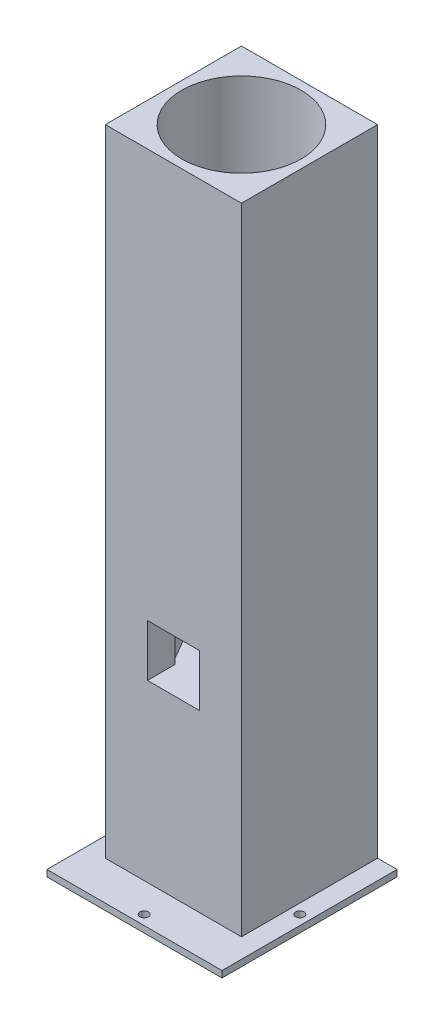
SolidWorks part; units mm, degrees
ref_plane "Front Plane" through (0, 0, 0) normal (0, 0, 1) x (1, 0, 0)
ref_plane "Top Plane" through (0, 0, 0) normal (0, 1, 0) x (1, 0, 0)
ref_plane "Right Plane" through (0, 0, 0) normal (1, 0, 0) x (0, 0, -1)
sketch "Sketch2" plane through (0, 0, 0) normal (0, 1, 0) x (1, 0, 0)
  line L0 (-7.1, 17.2376) -> (7.1, 17.2376)
  line L1 (11.3782, 14.7676) -> (18.4782, 2.47)
  line L2 (18.4782, -2.47) -> (11.3782, -14.7676)
  line L3 (7.1, -17.2376) -> (-7.1, -17.2376)
  line L4 (-11.3782, -14.7676) -> (-18.4782, -2.47)
  line L5 (-18.4782, 2.47) -> (-11.3782, 14.7676)
  line L6 (-7.1, 17.2376) -> (-11.3782, 14.7676)
  line L7 (11.3782, 14.7676) -> (7.1, 17.2376)
  line L8 (18.4782, -2.47) -> (18.4782, 2.47)
  line L9 (7.1, -17.2376) -> (11.3782, -14.7676)
  line L10 (-11.3782, -14.7676) -> (-7.1, -17.2376)
  line L11 (-18.4782, 2.47) -> (-18.4782, -2.47)
  line L13 (-26.25, -26.25) -> (26.25, -26.25)
  line L14 (-26.25, -26.25) -> (-26.25, 26.25)
  line L15 (-26.25, 26.25) -> (26.25, 26.25)
  line L16 (26.25, -26.25) -> (26.25, 26.25)
  line L17 (-26.25, -26.25) -> (26.25, 26.25) construction
  line L18 (-26.25, 26.25) -> (26.25, -26.25) construction
  circle A0 centre (0, 0) radius 28.6425
  circle A1 centre (0, 0) radius 18.6425 construction
  circle A2 centre (0, 0) radius 23
  point P5 (0, 17.2376)
  point P16 (0, 0)
  dimension "D5" = 10
  dimension "D6" = 46
  dimension "D7" = 52.5
  dimension "D1" = 14.2
  dimension "D2" = 4.94
  dimension "D3" = 6
  dimension "D8" = 52.5
  dimension "D4" = 6
extrude "Boss-Extrude1" add sketch "Sketch2" along normal blind 50 contours A0 A2 | A2 L11 L5 L6 L0 L7 L1 L8 L2 L9 L3 L10 L4 region at (-19.7283, 0, 19.7283) region at (-22.3495, 0, 0)
extrude "Boss-Extrude2" add sketch "Sketch2<3>" along normal blind 127.5 from surface contours A0 A2 region at (-19.7283, 0, 19.7283) starting at face at (0, 50, 0)
sketch "Sketch2<3>" plane through (0, 0, 0) normal (0, 1, 0) x (1, 0, 0) same geometry as "Sketch2"
extrude "Boss-Extrude3" add sketch "Sketch2<4>" along normal up to surface (177.5 mm away) contours A0 L15 L14 | A0 L16 L15 | A0 L13 L16 | A0 L14 L13 region at (-21.968, 0, 21.968) region at (21.968, 0, 21.968) region at (-21.968, 0, -21.968) region at (21.968, 0, -21.968) up to face at (0, 177.5, 0)
sketch "Sketch2<4>" plane through (0, 0, 0) normal (0, 1, 0) x (1, 0, 0) same geometry as "Sketch2"
sketch "Sketch3" plane through (0, 0, 0) normal (0, -1, 0) x (1, 0, 0)
  line L1 (-26.25, 26.25) -> (26.25, 26.25)
  line L2 (-26.25, 26.25) -> (-26.25, -26.25)
  line L3 (-26.25, -26.25) -> (26.25, -26.25)
  line L4 (26.25, 26.25) -> (26.25, -26.25)
extrude "Boss-Extrude4" add sketch "Sketch3" along normal blind 70
ref_plane "Plane1" through (0, -70, 0) normal (0, -1, 0) x (-1, 0, 0)
sketch "Sketch5" plane through (0, -70, 0) normal (0, -1, 0) x (1, 0, 0)
  line L0 (26.25, 26.25) -> (-26.25, 26.25) construction
  line L1 (-33.75, -26.25) -> (33.75, -26.25)
  line L2 (-33.75, -26.25) -> (-33.75, 41.25)
  line L3 (-33.75, 41.25) -> (33.75, 41.25)
  line L4 (33.75, -26.25) -> (33.75, 41.25)
  line L5 (-33.75, -26.25) -> (33.75, 41.25) construction
  line L6 (-33.75, 41.25) -> (33.75, -26.25) construction
  line L7 (-23.75, -23.75) -> (23.75, -23.75)
  line L8 (-23.75, -23.75) -> (-23.75, 23.75)
  line L9 (-23.75, 23.75) -> (23.75, 23.75)
  line L10 (23.75, -23.75) -> (23.75, 23.75)
  line L11 (-23.75, -23.75) -> (23.75, 23.75) construction
  line L12 (-23.75, 23.75) -> (23.75, -23.75) construction
  line L13 (0, -994.535) -> (0, 49005.465) construction
  line L14 (-26.25, -26.25) -> (26.25, -26.25) construction
  circle A1 centre (0, 37.5) radius 1.65
  circle A2 centre (-30, 7.5) radius 1.65
  circle A3 centre (30, 7.5) radius 1.65
  point P21 (0, 0)
  point P22 (0, 0)
  point P23 (0, 0)
  point P24 (33.75, 7.5)
  point P25 (0, 7.5)
  point P27 (0, 0)
  line M2 (-26.25, 26.25) -> (-26.25, -26.25)
  line M3 (-26.25, -26.25) -> (26.25, -26.25)
  line M4 (26.25, -26.25) -> (26.25, 26.25)
  line M10 (26.25, 26.25) -> (-26.25, 26.25)
  dimension "D5" = 3.3
  dimension "D7" = 3.3
  dimension "D2" = 67.5
  dimension "D3" = 67.5
  dimension "D4" = 2.5
  dimension "D6" = 3.75
  dimension "D8" = 3.75
sketch "Sketch6" plane through (0, 0, 26.25) normal (0, 0, 1) x (1, 0, 0)
  line L0 (37.125, 0) -> (-37.125, 0) construction
  line L1 (10, 20) -> (-10, 20)
  line L2 (10, 20) -> (10, 0)
  line L3 (10, 0) -> (-10, 0)
  line L4 (-10, 20) -> (-10, 0)
  point P6 (0, 20)
  dimension "D1" = 20
  dimension "D2" = 20
extrude "Cut-Extrude7" cut sketch "Sketch6" against normal blind 30
extrude "Boss-Extrude7" add sketch "Sketch5" against normal blind 2.5 contours L1 L4 L3 L2 M2 M10 M4 M3 region at (-32.7954, -70, 7.5)
sketch "Sketch8" plane through (0, -70, 0) normal (0, -1, 0) x (1, 0, 0)
  line L1 (-22.5, -22.5) -> (22.5, -22.5)
  line L2 (-22.5, -22.5) -> (-22.5, 22.5)
  line L3 (-22.5, 22.5) -> (22.5, 22.5)
  line L4 (22.5, -22.5) -> (22.5, 22.5)
  line L5 (-22.5, -22.5) -> (22.5, 22.5) construction
  line L6 (-22.5, 22.5) -> (22.5, -22.5) construction
  point P0 (0, 0)
  dimension "D1" = 45
  dimension "D2" = 45
extrude "Cut-Extrude9" cut sketch "Sketch8" against normal blind 60
